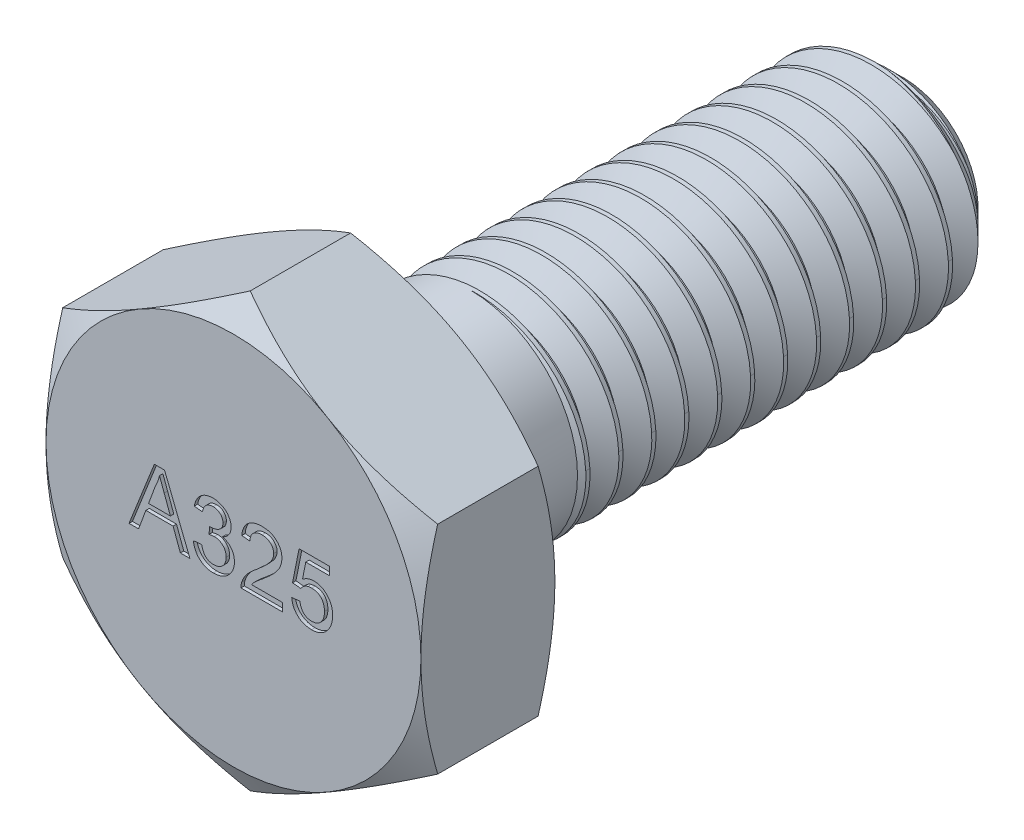
SolidWorks part; units mm, degrees
ref_plane "Front Plane" through (0, 0, 0) normal (0, 0, 1) x (1, 0, 0)
ref_plane "Top Plane" through (0, 0, 0) normal (0, 1, 0) x (1, 0, 0)
ref_plane "Right Plane" through (0, 0, 0) normal (1, 0, 0) x (0, 0, -1)
sketch "Sketch1" plane through (0, 0, 0) normal (1, 0, 0) x (0, 0, -1)
  line L0 (0, 0) -> (-7.9375, 0) construction
  line L1 (0, 0) -> (31.75, 0) construction
  line L2 (-7.9375, 11.1125) -> (-7.9375, -11.1125) construction
  line L3 (31.75, 6.35) -> (31.75, -6.35) construction
  line L4 (31.75, -6.35) -> (29.7962, -6.35) construction
  point P3 (6.35, 0)
  point P7 (-7.9375, 0)
  point P10 (31.75, 0)
  point P12 (0, 11.1125)
  point P13 (20.5154, -6.35)
  point P14 (31.75, 6.35)
  point P15 (31.75, -6.35)
  point P16 (-7.9375, 11.1125)
  point P18 (6.35, 6.35)
  point P20 (0, -11.1125)
  point P22 (-7.9375, -11.1125)
  dimension "Hex Size" = 22.225
  dimension "Head Height" = 7.9375
  dimension "Grip Length" = 6.35
  dimension "Length" = 31.75
  dimension "Thread Pitch" = 1.9538
  dimension "Screw Size Decimal Equivalent" = 12.7
  dimension "Minimum Thread Length" = 25.4
  dimension "D2" = 11.2346
sketch "Sketch14" plane through (0, 0, 0) normal (0, 0, 1) x (1, 0, 0)
  line L0 (-11.1125, 0) -> (11.1125, 0)
  line L1 (0, 11.1125) -> (0, -11.1125) construction
  point P4 (0, 0)
  dimension "Head Width" = 22.225
sketch "Sketch2" plane through (0, 0, 0) normal (0, 0, 1) x (1, 0, 0)
  line L1 (0, 12.8316) -> (-11.1125, 6.4158)
  line L2 (-11.1125, 6.4158) -> (-11.1125, -6.4158)
  line L3 (-11.1125, -6.4158) -> (0, -12.8316)
  line L4 (0, -12.8316) -> (11.1125, -6.4158)
  line L5 (11.1125, -6.4158) -> (11.1125, 6.4158)
  line L6 (11.1125, 6.4158) -> (0, 12.8316)
  circle A0 centre (0, 0) radius 11.1125 construction
extrude "Boss-Extrude1" add sketch "Sketch2" along normal up to vertex (7.9375 mm away) up to point (0, 0, 7.9375)
sketch "Sketch3" plane through (0, 0, 7.9375) normal (0, 0, 1) x (1, 0, 0)
  line L0 (11.1125, 6.4158) -> (0, 12.8316) construction
  circle A0 centre (0, 0) radius 11.1125
extrude "Cut-Extrude1" cut sketch "Sketch3" against normal through all draft 60 flip side to cut
sketch "Sketch4" plane through (0, 0, 0) normal (0, 0, -1) x (-1, 0, 0)
  circle A0 centre (0, 0) radius 11.1125 construction
  circle A1 centre (0, 0) radius 11.1125
extrude "Cut-Extrude2" cut sketch "Sketch4" against normal through all draft 60 flip side to cut
sketch "Sketch5" plane through (0, 0, 0) normal (0, 0, -1) x (-1, 0, 0)
  circle A0 centre (0, 0) radius 6.35
extrude "Boss-Extrude2" add sketch "Sketch5" along normal up to vertex (31.75 mm away) up to point (0, 0, -31.75)
chamfer "Chamfer1" distance 1.905 angle 45 1 edges at (-6.35, 0, -31.75)
sketch "Sketch13" plane through (0, 0, 7.9375) normal (0, 0, 1) x (1, 0, 0)
  arc A6 (5.5562, -9.6237) -> (11.1125, 0) centre (0, 0) ccw
  arc A7 (11.1125, 0) -> (5.5562, 9.6237) centre (0, 0) ccw
  arc A8 (5.5562, 9.6237) -> (-5.5562, 9.6237) centre (0, 0) ccw
  arc A9 (-5.5562, 9.6237) -> (-11.1125, 0) centre (0, 0) ccw
  arc A10 (-11.1125, 0) -> (-5.5562, -9.6237) centre (0, 0) ccw
  arc A11 (-5.5562, -9.6237) -> (5.5562, -9.6237) centre (0, 0) ccw
  arc A12 (5.5562, -9.6237) -> (11.1125, 0) centre (0, 0) ccw
  arc A13 (11.1125, 0) -> (5.5562, 9.6237) centre (0, 0) ccw
  arc A14 (5.5562, 9.6237) -> (-5.5562, 9.6237) centre (0, 0) ccw
  arc A15 (-5.5562, 9.6237) -> (-11.1125, 0) centre (0, 0) ccw
  arc A16 (-11.1125, 0) -> (-5.5562, -9.6237) centre (0, 0) ccw
  arc A17 (-5.5562, -9.6237) -> (5.5562, -9.6237) centre (0, 0) ccw
  dimension "D1" = 0
extrude "Boss-Extrude5" add sketch "Sketch13" along normal blind 0.381 separate body
sketch "Sketch6" plane through (0, 0, 8.3185) normal (0, 0, 1) x (1, 0, 0)
  line L0 (-11.1125, 0) -> (11.1125, 0) construction
  line L1 (-11.1125, 0) -> (-11.1125, -6.4158) construction
  line L2 (11.1125, -2.54) -> (-11.1125, -2.54) construction
  line L3 (11.1125, -6.4158) -> (11.1125, 0) construction
  text T0 "A325" font "Arial" height in points 22
  point P4 (0, 0)
  dimension "D1" = 2.54
extrude "Boss-Extrude4" add sketch "Sketch6" against normal offset from surface (0.762 mm away) 0.381 up to face at (11.1125, 0, 7.9375) offset beyond the face yes
scale "Scale1" bodies to scale 114 scale about centroid uniform scaling no x scale factor 0.67 y scale factor 0.67 z scale factor 0.67
combine bodies "Combine1" operation type subtract main body 107 bodies to subtract 115 115 115 115
sketch "Sketch7" plane through (0, 0, -31.75) normal (0, 0, -1) x (-1, 0, 0)
  circle A0 centre (0, 0) radius 6.35 construction
  circle A1 centre (0, 0) radius 6.35
curve "Helix/Spiral1" pitch 1.9538 height 27.3538 radius 6.35 centre (0, 0, -31.75) axis (0, 0, 1) start towards (0, 1, 0)
sketch "Sketch9" plane through (0, 0, 0) normal (1, 0, 0) x (0, 0, -1)
  line L0 (33.5817, 6.5615) -> (31.6279, 6.5615) construction
  line L1 (31.6279, 6.5615) -> (32.6048, 4.8694) construction
  line L2 (32.6048, 4.8694) -> (33.5817, 6.5615) construction
  line L3 (33.4596, 6.35) -> (31.75, 6.35) construction
  line L4 (32.6048, 6.5615) -> (32.6048, 6.35) construction
  line L5 (33.5207, 6.4558) -> (31.6889, 6.4558) construction
  line L6 (32.7269, 5.0809) -> (32.4827, 5.0809) construction
  line L7 (32.6048, 5.0809) -> (32.6048, 4.8694) construction
  line L8 (31.6889, 6.4558) -> (33.5207, 6.4558)
  line L9 (33.5207, 6.4558) -> (32.7269, 5.0809)
  line L10 (32.7269, 5.0809) -> (32.4827, 5.0809)
  line L11 (32.4827, 5.0809) -> (31.6889, 6.4558)
  point P13 (32.6048, 6.4558)
  dimension "D1" = 1.9538
  dimension "D2" = 0.2442
sweep "Cut-Sweep1" cut profiles "Sketch9" path "Helix/Spiral1" align with end faces yes
ref_plane "Plane1" through (0, 0, -4.3962) normal (0, 0, 1) x (1, 0, 0)
sketch "Sketch10" plane through (0, 0, -4.3962) normal (0, 0, 1) x (1, 0, 0)
  circle A0 centre (0, 0) radius 6.35 construction
  circle A1 centre (0, 0) radius 6.35
extrude "Boss-Extrude3" add sketch "Sketch10" against normal up to vertex (1.7096 mm away) up to point (0, 6.35, -6.1058)
equation "\"D1@Chamfer1\" = \"Screw Size Decimal Equivalent@Sketch1\" * .15"
equation "\"D4@Helix/Spiral1\" = \"Thread Pitch@Sketch1\""
equation "\"D3@Helix/Spiral1\" = \"Minimum Thread Length@Sketch1\" + \"Thread Pitch@Sketch1\""
equation "\"D1@Sketch9\" = \"Thread Pitch@Sketch1\""
equation "\"D2@Sketch9\"=\"D1@Sketch9\" / 1/8"
equation "\"D2@Sketch1\" = \"Thread Pitch@Sketch1\" * 5.75"
